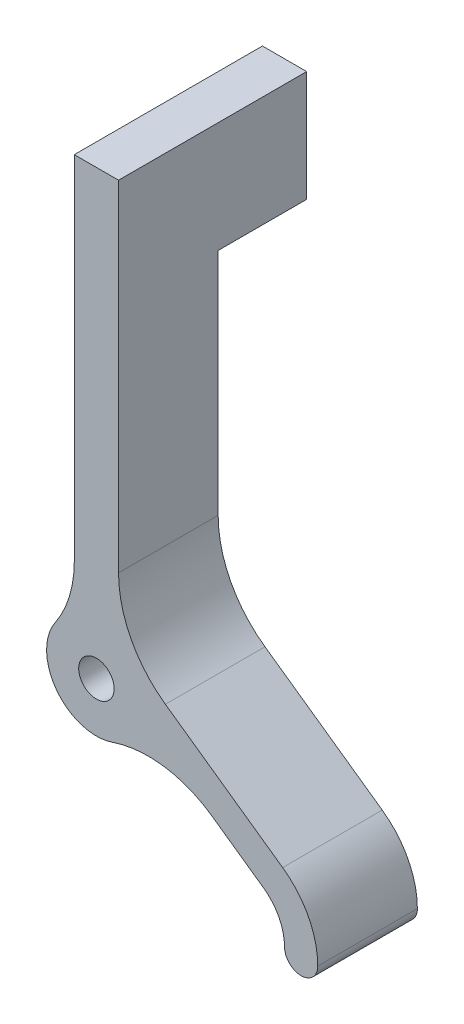
SolidWorks part; units mm, degrees
ref_plane "Front Plane" through (0, 0, 0) normal (0, 0, 1) x (1, 0, 0)
ref_plane "Top Plane" through (0, 0, 0) normal (0, 1, 0) x (1, 0, 0)
ref_plane "Right Plane" through (0, 0, 0) normal (1, 0, 0) x (0, 0, -1)
sketch "Sketch1" plane through (0, 0, 0) normal (0, 0, 1) x (1, 0, 0)
  line L0 (2.5958, 3.6758) -> (16.8264, -6.3736)
  line L2 (15.0958, -8.8242) -> (4.3309, -1.2221)
  line L3 (2, 4.0311) -> (2, 40)
  line L4 (2, 40) -> (-2, 40)
  line L5 (-2, 40) -> (-2, 4.0311)
  circle A0 centre (0, 0) radius 1.6
  arc A1 (2.5958, 3.6758) -> (2, 4.0311) centre (0, 0) ccw
  arc A2 (-2, 4.0311) -> (4.3309, -1.2221) centre (0, 0) ccw
  arc A4 (15.0958, -8.8242) -> (17, -12.5) centre (12.5, -12.5) cw
  arc A5 (17, -12.5) -> (20, -12.5) centre (18.5, -12.5) ccw
  arc A6 (16.8264, -6.3736) -> (20, -12.5) centre (12.5, -12.5) cw
  circle A7 centre (12.5, -12.5) radius 4.5 construction
  point P3 (0, 0)
  point P10 (0, 40)
  point P13 (14.0363, -8.2704)
  point P19 (0, 0)
  point P20 (0, 0)
  point P21 (0, 0)
  point P23 (11.327, -13.073)
  point P24 (4.3266, -1.2372)
  dimension "D1" = 3.2
  dimension "D2" = 4.5
  dimension "D8" = 12.5
  dimension "D5" = 1.5
  dimension "D9" = 9
  dimension "D3" = 3
  dimension "D4" = 12.5
  dimension "D6" = 4
  dimension "D7" = 40
extrude "Boss-Extrude1" add sketch "Sketch1" along normal blind 9
fillet "Fillet1" radius 10 3 edges at (4.3309, -1.2221, 4.5) (-2, 4.0311, 4.5) (2, 4.0311, 4.5)
sketch "Sketch2" plane through (0, 0, 0) normal (0, 0, -1) x (-1, 0, 0)
  line L0 (-2, 9.2769) -> (-2, 40) construction
  line L1 (2, 40) -> (-2, 40)
  line L2 (2, 40) -> (2, 30)
  line L3 (2, 30) -> (-2, 30)
  line L4 (-2, 40) -> (-2, 30)
  dimension "D1" = 10
extrude "Boss-Extrude2" add sketch "Sketch2" along normal blind 8
